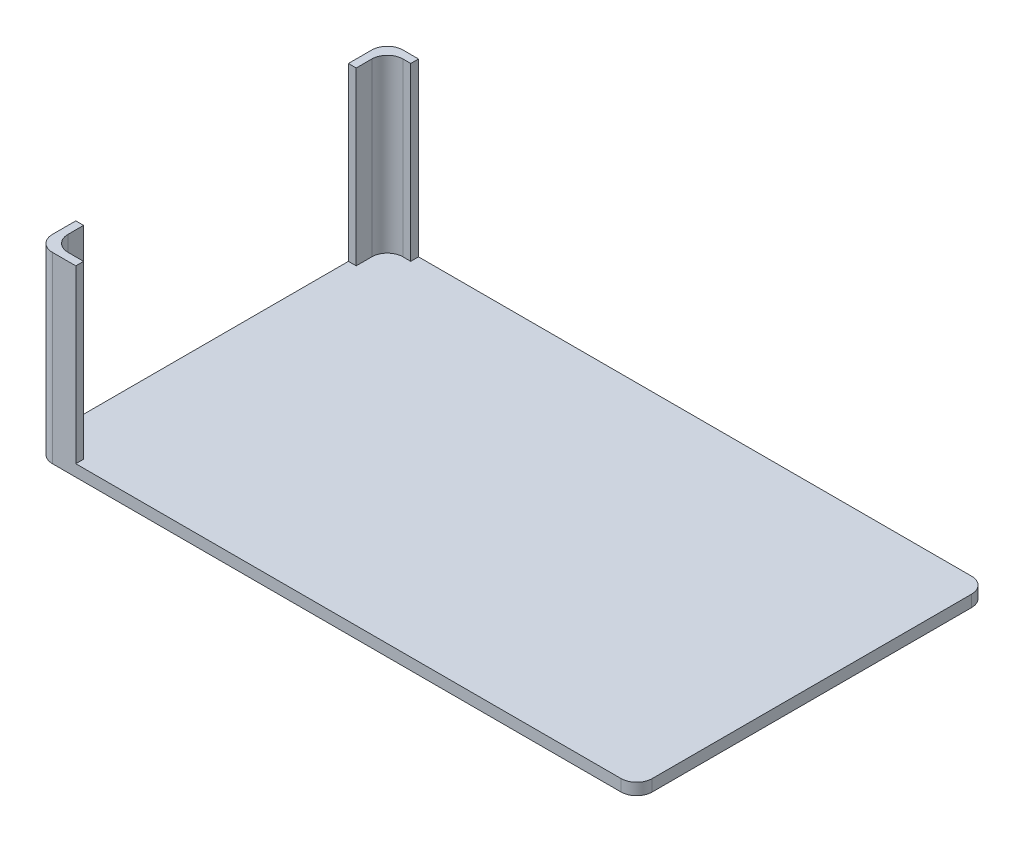
SolidWorks part; units mm, degrees
ref_plane "Спереди" through (0, 0, 0) normal (0, 0, 1) x (1, 0, 0)
ref_plane "Сверху" through (0, 0, 0) normal (0, 1, 0) x (1, 0, 0)
ref_plane "Справа" through (0, 0, 0) normal (1, 0, 0) x (0, 0, -1)
sketch "Эскиз3" plane through (0, 0, 0) normal (0, 1, 0) x (1, 0, 0)
  line L0 (-36, 16) -> (37, 16)
  line L1 (-38, 14) -> (-38, -27)
  line L2 (-36, -29) -> (37, -29)
  line L3 (39, 14) -> (39, -27)
  line L4 (34, -29) -> (34, -28)
  line L5 (-35, -28) -> (36, -28)
  line L6 (-37, -26) -> (-37, 13)
  line L7 (-35, 15) -> (36, 15)
  line L8 (38, -26) -> (38, 13)
  line L9 (38, -25) -> (39, -25)
  line L10 (-33, -29) -> (-33, -28)
  line L11 (-38, -24) -> (-37, -24)
  line L12 (-38, 11) -> (-37, 11)
  line L13 (-34, 15) -> (-34, 16)
  line L14 (38, 12) -> (39, 12)
  line L15 (35, 15) -> (35, 16)
  arc A0 (37, 16) -> (39, 14) centre (37, 14) cw
  arc A1 (39, -27) -> (37, -29) centre (37, -27) cw
  arc A2 (-38, -27) -> (-36, -29) centre (-36, -27) ccw
  arc A3 (-38, 14) -> (-36, 16) centre (-36, 14) cw
  arc A4 (38, 13) -> (36, 15) centre (36, 13) ccw
  arc A5 (38, -26) -> (36, -28) centre (36, -26) cw
  arc A6 (-35, 15) -> (-37, 13) centre (-35, 13) ccw
  arc A7 (-37, -26) -> (-35, -28) centre (-35, -26) ccw
  point P41 (34, -28)
  dimension "D5" = 2
  dimension "D6" = 2
  dimension "D7" = 2
  dimension "D12" = 2
  dimension "D1" = 45
  dimension "D2" = 77
  dimension "D3" = 38
  dimension "D4" = 16
  dimension "D8" = 1
  dimension "D9" = 1
  dimension "D10" = 1
  dimension "D11" = 1
  dimension "D13" = 2
  dimension "D14" = 2
  dimension "D15" = 2
  dimension "D16" = 1
  dimension "D17" = 1
  dimension "D18" = 1
  dimension "D19" = 1
  dimension "D20" = 2
extrude "Бобышка-Вытянуть1" add sketch "Эскиз3" along normal blind 23.5 contours L6 A6 L7 A4 L8 A5 L5 A7 | L1 A2 L2 A1 L3 A0 L0 A3
extrude "Бобышка-Вытянуть2" add sketch "Эскиз3<3>" along normal blind 1.5 contours L6 A7 L5 A5 L8 A4 L7 A6 | L12 L1 L11 L6 | L7 L15 L0 L13 | L10 L2 L4 L5 | L14 L8 L9 L3 region at (0.5, 0, -15.5) region at (0.5, 0, 6.5) region at (-37.5, 0, 6.5) region at (38.5, 0, 6.5) region at (0.5, 0, 28.5)
sketch "Эскиз3<3>" plane through (0, 0, 0) normal (0, 1, 0) x (1, 0, 0) same geometry as "Эскиз3"
sketch "Эскиз6" plane through (0, 23.5, 0) normal (0, 1, 0) x (1, 0, 0)
  line L0 (-38, -24) -> (-37, -24) construction
  line L1 (-33, -29) -> (-33, -28) construction
  line L2 (38, -25) -> (39, -25) construction
  line L3 (34, -29) -> (34, -28) construction
  line L4 (-38, 14) -> (-38, -27)
  line L5 (-36, -29) -> (37, -29)
  line L6 (39, -27) -> (39, 14)
  line L7 (37, 16) -> (-36, 16)
  line L8 (-38, 14) -> (-38, -27)
  line L9 (-36, -29) -> (37, -29)
  line L10 (39, -27) -> (39, 14)
  line L11 (37, 16) -> (-36, 16)
  line L12 (37, 16) -> (-36, 16)
  line L13 (39, -27) -> (39, 14)
  line L14 (-36, -29) -> (37, -29)
  line L15 (-38, 14) -> (-38, -27)
  line L16 (37, 16) -> (-36, 16)
  line L17 (39, -27) -> (39, 14)
  line L18 (-36, -29) -> (37, -29)
  line L19 (-38, 14) -> (-38, -27)
  line L20 (-35, -28) -> (36, -28)
  line L21 (38, -26) -> (38, 13)
  line L22 (36, 15) -> (-35, 15)
  line L23 (-37, 13) -> (-37, -26)
  line L24 (-35, -28) -> (36, -28)
  line L25 (38, -26) -> (38, 13)
  line L26 (36, 15) -> (-35, 15)
  line L27 (-37, 13) -> (-37, -26)
  line L28 (35, 15) -> (35, 16) construction
  line L29 (38, 12) -> (39, 12) construction
  line L30 (-34, 15) -> (-34, 16) construction
  line L31 (-38, 11) -> (-37, 11) construction
  line L32 (-38, -24) -> (-37, -24)
  line L33 (-33, -29) -> (-33, -28)
  line L34 (38, -25) -> (39, -25)
  line L35 (34, -29) -> (34, -28)
  line L36 (35, 15) -> (35, 16)
  line L37 (38, 12) -> (39, 12)
  line L38 (-34, 15) -> (-34, 16)
  line L39 (-38, 11) -> (-37, 11)
  line L40 (34, -29) -> (-33, -29)
  line L41 (-33, -28) -> (34, -28)
  line L42 (-34, 15) -> (35, 15)
  line L43 (35, 16) -> (-34, 16)
  arc A4 (-36, 16) -> (-38, 14) centre (-36, 14) ccw
  arc A5 (-38, -27) -> (-36, -29) centre (-36, -27) ccw
  arc A6 (37, -29) -> (39, -27) centre (37, -27) ccw
  arc A7 (39, 14) -> (37, 16) centre (37, 14) ccw
  arc A8 (-36, 16) -> (-38, 14) centre (-36, 14) ccw
  arc A9 (-38, -27) -> (-36, -29) centre (-36, -27) ccw
  arc A10 (37, -29) -> (39, -27) centre (37, -27) ccw
  arc A11 (39, 14) -> (37, 16) centre (37, 14) ccw
  arc A12 (39, 14) -> (37, 16) centre (37, 14) ccw
  arc A13 (37, -29) -> (39, -27) centre (37, -27) ccw
  arc A14 (-38, -27) -> (-36, -29) centre (-36, -27) ccw
  arc A15 (-36, 16) -> (-38, 14) centre (-36, 14) ccw
  arc A16 (39, 14) -> (37, 16) centre (37, 14) ccw
  arc A17 (37, -29) -> (39, -27) centre (37, -27) ccw
  arc A18 (-38, -27) -> (-36, -29) centre (-36, -27) ccw
  arc A19 (-36, 16) -> (-38, 14) centre (-36, 14) ccw
  arc A20 (36, -28) -> (38, -26) centre (36, -26) ccw
  arc A21 (38, 13) -> (36, 15) centre (36, 13) ccw
  arc A22 (-35, 15) -> (-37, 13) centre (-35, 13) ccw
  arc A23 (-37, -26) -> (-35, -28) centre (-35, -26) ccw
  arc A24 (36, -28) -> (38, -26) centre (36, -26) ccw
  arc A25 (38, 13) -> (36, 15) centre (36, 13) ccw
  arc A26 (-35, 15) -> (-37, 13) centre (-35, 13) ccw
  arc A27 (-37, -26) -> (-35, -28) centre (-35, -26) ccw
  dimension "D1" = 0
  dimension "D2" = 0
  dimension "D3" = 0
extrude "Вырез-Вытянуть1" cut sketch "Эскиз6" against normal blind 22 contours L37 L25 L34 L17 | L39 L19 L32 L27 | L18 L35 L24 L33 | L38 L26 L36 L16 region at (-37.5, 23.5, 6.5) region at (0.5, 23.5, -15.5) region at (0.5, 23.5, 28.5) region at (38.5, 23.5, 6.5)
sketch "Эскиз9" plane through (0, 23.5, 0) normal (0, 1, 0) x (1, 0, 0)
  line L6 (38, 12) -> (39, 12)
  line L7 (39, 12) -> (39, 14)
  line L8 (37, 16) -> (35, 16)
  line L9 (35, 16) -> (35, 15)
  line L10 (35, 15) -> (36, 15)
  line L11 (38, 13) -> (38, 12)
  line L12 (38, 12) -> (39, 12)
  line L13 (39, 12) -> (39, 14)
  line L14 (37, 16) -> (35, 16)
  line L15 (35, 16) -> (35, 15)
  line L16 (35, 15) -> (36, 15)
  line L17 (38, 13) -> (38, 12)
  line L18 (39, -27) -> (39, -25)
  line L19 (39, -25) -> (38, -25)
  line L20 (38, -25) -> (38, -26)
  line L21 (36, -28) -> (34, -28)
  line L22 (34, -28) -> (34, -29)
  line L23 (34, -29) -> (37, -29)
  line L24 (39, -27) -> (39, -25)
  line L25 (39, -25) -> (38, -25)
  line L26 (38, -25) -> (38, -26)
  line L27 (36, -28) -> (34, -28)
  line L28 (34, -28) -> (34, -29)
  line L29 (34, -29) -> (37, -29)
  arc A2 (39, 14) -> (37, 16) centre (37, 14) ccw
  arc A3 (38, 13) -> (36, 15) centre (36, 13) ccw
  arc A4 (39, 14) -> (37, 16) centre (37, 14) ccw
  arc A5 (38, 13) -> (36, 15) centre (36, 13) ccw
  arc A6 (36, -28) -> (38, -26) centre (36, -26) ccw
  arc A7 (37, -29) -> (39, -27) centre (37, -27) ccw
  arc A8 (36, -28) -> (38, -26) centre (36, -26) ccw
  arc A9 (37, -29) -> (39, -27) centre (37, -27) ccw
  dimension "D1" = 0
  dimension "D2" = 0
extrude "Вырез-Вытянуть2" cut sketch "Эскиз9" against normal blind 22
